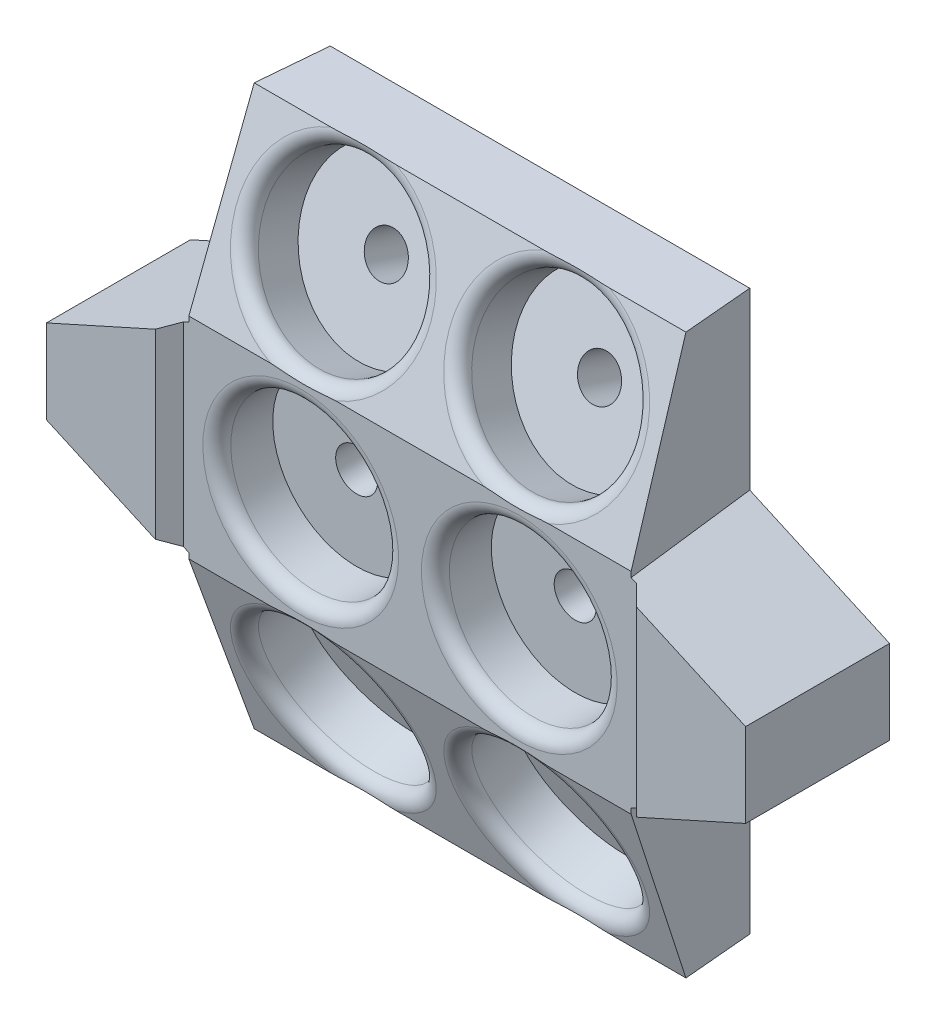
SolidWorks part; units mm, degrees
ref_plane "Front Plane" through (0, 0, 0) normal (0, 0, 1) x (1, 0, 0)
ref_plane "Top Plane" through (0, 0, 0) normal (0, 1, 0) x (1, 0, 0)
ref_plane "Right Plane" through (0, 0, 0) normal (1, 0, 0) x (0, 0, -1)
sketch "Sketch2" plane through (0, 0, 0) normal (0, 1, 0) x (1, 0, 0)
  line L0 (0, 0) -> (30, 0)
  line L1 (30, 0) -> (30.8749, -10)
  line L2 (30.8749, -10) -> (-0.8749, -10)
  line L3 (-0.8749, -10) -> (0, 0)
  dimension "D1" = 95
  dimension "D2" = 95
  dimension "D3" = 30
  dimension "D4" = 10
extrude "Boss-Extrude1" add sketch "Sketch2" along normal blind 40
sketch "Sketch3" plane through (0, 0, 0) normal (1, 0, 0) x (0, 0, -1)
  line L0 (-5, 0) -> (-9.2975, 12.4808)
  line L1 (0, 0) -> (-10, 0) construction
  line L2 (-9.2975, 12.4808) -> (-9.2975, 27.5192)
  line L3 (-9.2975, 27.5192) -> (-5, 40)
  line L4 (0, 40) -> (-10, 40) construction
  line L5 (-5, 0) -> (-10, 0)
  line L6 (-10, 0) -> (-10, 40)
  line L7 (-10, 40) -> (-5, 40)
  dimension "D1" = 161
  dimension "D2" = 161
  dimension "D3" = 13.2
  dimension "D4" = 5
extrude "Cut-Extrude1" cut sketch "Sketch3" against normal through all both and the other way through all
sketch "Sketch5" plane through (0, -1.5392, 4.47) normal (0, -0.3256, 0.9455) x (1, 0, 0)
  line L0 (7.3746, 8.2278) -> (-0.6254, 8.2278) construction
  line L1 (-0.4374, 1.6278) -> (-0.8134, 14.8278) construction
  line L2 (22.6254, 8.2278) -> (30.6254, 8.2278) construction
  line L3 (30.8134, 14.8278) -> (30.4374, 1.6278) construction
  line L4 (7.3746, 8.2278) -> (22.6254, 8.2278) construction
  line L5 (-0.4374, 1.6278) -> (30.4374, 1.6278) construction
  circle A0 centre (7.3746, 8.2278) radius 6
  circle A1 centre (22.6254, 8.2278) radius 6
  dimension "D1" = 12
  dimension "D2" = 8
  dimension "D3" = 6.6
extrude "Cut-Extrude2" cut sketch "Sketch5" against normal blind 4
ref_plane "Plane1" through (0, 20, 0) normal (0, 1, 0) x (1, 0, 0)
mirror "Mirror3" about plane through (0, 20, 0) normal (0, 1, 0) of "Cut-Extrude2"
sketch "Sketch7" plane through (0, 0, 9.2975) normal (0, 0, 1) x (1, 0, 0)
  line L0 (-0.8134, 20) -> (30.8134, 20) construction
  line L1 (-0.8134, 12.4808) -> (-0.8134, 27.5192) construction
  line L2 (30.8134, 27.5192) -> (30.8134, 12.4808) construction
  circle A0 centre (7.1866, 20) radius 6
  circle A1 centre (22.8134, 20) radius 6
  dimension "D1" = 12
  dimension "D2" = 8
  dimension "D3" = 8
extrude "Cut-Extrude3" cut sketch "Sketch7" against normal blind 4
fillet "Fillet1" radius 1 6 edges at (22.6254, 0.5673, 5.1953) (7.3746, 0.5673, 5.1953) (13.1866, 20, 9.2975) (28.8134, 20, 9.2975) (7.3746, 39.4327, 5.1953) (22.6254, 39.4327, 5.1953)
sketch "Sketch9" plane through (0, 0, 0) normal (0, 0, -1) x (-1, 0, 0)
  line L0 (-30, 12.5) -> (-40, 17)
  line L1 (-30, 40) -> (-30, 0) construction
  line L2 (-40, 17) -> (-40, 23)
  line L3 (-40, 23) -> (-30, 27.5)
  line L4 (-30, 27.5) -> (-30, 12.5)
  line L5 (0, 12.5) -> (0, 27.5)
  line L6 (0, 40) -> (0, 0) construction
  line L7 (0, 27.5) -> (10, 23)
  line L8 (10, 23) -> (10, 17)
  line L9 (10, 17) -> (0, 12.5)
  line L10 (-40, 20) -> (10, 20) construction
  point P4 (-30, 20)
  point P13 (0, 20)
  dimension "D1" = 10
  dimension "D2" = 10
  dimension "D3" = 15
  dimension "D4" = 15
  dimension "D5" = 6
  dimension "D6" = 6
extrude "Boss-Extrude2" add sketch "Sketch9" against normal blind 6
sketch "Sketch10" plane through (0, 0, 0) normal (0, 0, -1) x (-1, 0, 0)
  line L0 (-15, 40) -> (-15, 0) construction
  line L1 (-30, 40) -> (0, 40) construction
  line L2 (-30, 0) -> (0, 0) construction
  line L3 (-30, 40) -> (0, 0) construction
  line L4 (-15, 20) -> (10, 20) construction
  line L5 (10, 17) -> (10, 23) construction
  line L6 (-15, 20) -> (-40, 20) construction
  line L7 (-40, 23) -> (-40, 17) construction
  circle A0 centre (-15, 20) radius 15 construction
  circle A1 centre (-15, 37.5) radius 2.1
  circle A2 centre (-15, 2.5) radius 2.1
  circle A3 centre (-35, 20) radius 2.1
  circle A4 centre (5, 20) radius 2.1
  dimension "D1" = 30
  dimension "D2" = 4.2
  dimension "D3" = 20
  dimension "D4" = 20
  dimension "D5" = 17.5
  dimension "D6" = 17.5
extrude "Cut-Extrude5" cut sketch "Sketch10" against normal blind 4
sketch "Sketch11" plane through (0, 0, 5.2975) normal (0, 0, 1) x (1, 0, 0)
  circle A0 centre (7.1866, 20) radius 1.5
  circle A1 centre (22.8134, 20) radius 1.5
  dimension "D1" = 3
  dimension "D2" = 3
extrude "Cut-Extrude6" cut sketch "Sketch11" against normal up to next
sketch "Sketch12" plane through (0, -0.2369, 0.688) normal (0, -0.3256, 0.9455) x (1, 0, 0)
  circle A0 centre (7.3746, 8.2278) radius 1.5
  circle A1 centre (22.6254, 8.2278) radius 1.5
  dimension "D1" = 3
  dimension "D2" = 3
extrude "Cut-Extrude7" cut sketch "Sketch12" against normal up to next
sketch "Sketch13" plane through (0, 4.4767, 13.0012) normal (0, 0.3256, 0.9455) x (1, 0, 0)
  circle A0 centre (22.6254, 29.5929) radius 1.5
  circle A1 centre (7.3746, 29.5929) radius 1.5
  dimension "D1" = 3
  dimension "D2" = 3
extrude "Cut-Extrude8" cut sketch "Sketch13" against normal up to next
sketch "Sketch15" plane through (0, 0, 6) normal (0, 0, 1) x (1, 0, 0)
  line L4 (30.5249, 27.2638) -> (30.5249, 12.7362)
  line L5 (30.5249, 12.7362) -> (40, 17)
  line L6 (40, 17) -> (40, 23)
  line L7 (40, 23) -> (30.5249, 27.2638)
  line L8 (30.5249, 27.2638) -> (30.5249, 12.7362)
  line L9 (30.5249, 12.7362) -> (40, 17)
  line L10 (40, 17) -> (40, 23)
  line L11 (40, 23) -> (30.5249, 27.2638)
  line L12 (-0.5249, 12.7362) -> (-0.5249, 27.2638)
  line L13 (-0.5249, 27.2638) -> (-10, 23)
  line L14 (-10, 23) -> (-10, 17)
  line L15 (-10, 17) -> (-0.5249, 12.7362)
  line L16 (-0.5249, 12.7362) -> (-0.5249, 27.2638)
  line L17 (-0.5249, 27.2638) -> (-10, 23)
  line L18 (-10, 23) -> (-10, 17)
  line L19 (-10, 17) -> (-0.5249, 12.7362)
  dimension "D1" = 0
  dimension "D2" = 0
extrude "Boss-Extrude3" add sketch "Sketch15" along normal up to surface (3.2975 mm away) up to face at (7.1866, 27, 9.2975)
sketch "Sketch17" plane through (0, 0, 9.2975) normal (0, 0, 1) x (1, 0, 0)
  line L0 (31.2134, 13.046) -> (31.2134, 26.954)
  line L1 (-1.2134, 13.046) -> (-1.2134, 26.954)
  line L2 (-0.8134, 12.866) -> (-10, 17) construction
  line L16 (-0.8134, 27.5192) -> (-0.8134, 27.134)
  line L17 (-0.8134, 27.134) -> (-10, 23)
  line L18 (-10, 23) -> (-10, 17)
  line L19 (-10, 17) -> (-0.8134, 12.866)
  line L20 (-0.8134, 12.866) -> (-0.8134, 12.4808)
  line L21 (-0.8134, 12.4808) -> (5.0422, 12.4808)
  line L22 (9.7069, 12.4808) -> (20.2931, 12.4808)
  line L23 (24.9578, 12.4808) -> (30.8134, 12.4808)
  line L24 (30.8134, 12.4808) -> (30.8134, 12.866)
  line L25 (30.8134, 12.866) -> (40, 17)
  line L26 (40, 17) -> (40, 23)
  line L27 (40, 23) -> (30.8134, 27.134)
  line L28 (30.8134, 27.134) -> (30.8134, 27.5192)
  line L29 (30.8134, 27.5192) -> (24.9578, 27.5192)
  line L30 (20.2931, 27.5192) -> (9.7069, 27.5192)
  line L31 (5.0422, 27.5192) -> (-0.8134, 27.5192)
  line L32 (-0.8134, 27.5192) -> (-0.8134, 27.134)
  line L33 (-0.8134, 27.134) -> (-10, 23)
  line L34 (-10, 23) -> (-10, 17)
  line L35 (-10, 17) -> (-0.8134, 12.866)
  line L36 (-0.8134, 12.866) -> (-0.8134, 12.4808)
  line L37 (-0.8134, 12.4808) -> (5.0422, 12.4808)
  line L38 (9.7069, 12.4808) -> (20.2931, 12.4808)
  line L39 (24.9578, 12.4808) -> (30.8134, 12.4808)
  line L40 (30.8134, 12.4808) -> (30.8134, 12.866)
  line L41 (30.8134, 12.866) -> (40, 17)
  line L42 (40, 17) -> (40, 23)
  line L43 (40, 23) -> (30.8134, 27.134)
  line L44 (30.8134, 27.134) -> (30.8134, 27.5192)
  line L45 (30.8134, 27.5192) -> (24.9578, 27.5192)
  line L46 (20.2931, 27.5192) -> (9.7069, 27.5192)
  line L47 (5.0422, 27.5192) -> (-0.8134, 27.5192)
  spline S4 degree 3 poles (-208.2366, 3004.6079) (-16.3502, 9.5456) (-5.3981, 11.6237) (5.82, 12.5282) (6.0142, 12.5451) (6.5971, 12.5879) (6.987, 12.6056) (7.7657, 12.6055) (8.1543, 12.5878) (8.7364, 12.545) (8.9303, 12.5281) (20.1553, 11.6233) (31.1363, 9.6302) (178.0376, 3007.4811) knots -6.969546 -6.969546 -6.969546 -6.969546 0.125 0.125 0.25 0.25 0.5 0.5 0.75 0.75 0.875 0.875 7.983441 7.983441 7.983441 7.983441 only from (5.0422, 12.4808) to (9.7069, 12.4808)
  spline S5 degree 3 poles (-192.9858, 3004.6079) (-1.0994, 9.5456) (9.8528, 11.6237) (21.0709, 12.5282) (21.2651, 12.5451) (21.848, 12.5879) (22.2379, 12.6056) (23.0166, 12.6055) (23.4052, 12.5878) (23.9873, 12.545) (24.1812, 12.5281) (35.4062, 11.6233) (46.3872, 9.6302) (193.2884, 3007.4811) knots -6.969546 -6.969546 -6.969546 -6.969546 0.125 0.125 0.25 0.25 0.5 0.5 0.75 0.75 0.875 0.875 7.983441 7.983441 7.983441 7.983441 only from (20.2931, 12.4808) to (24.9578, 12.4808)
  spline S6 degree 3 poles (238.2366, -2964.6079) (46.3502, 30.4544) (35.3981, 28.3763) (24.18, 27.4718) (23.9858, 27.4549) (23.4029, 27.4121) (23.013, 27.3944) (22.2343, 27.3945) (21.8457, 27.4122) (21.2636, 27.455) (21.0697, 27.4719) (9.8447, 28.3767) (-1.1363, 30.3698) (-148.0376, -2967.4811) knots -6.969546 -6.969546 -6.969546 -6.969546 0.125 0.125 0.25 0.25 0.5 0.5 0.75 0.75 0.875 0.875 7.983441 7.983441 7.983441 7.983441 only from (24.9578, 27.5192) to (20.2931, 27.5192)
  spline S7 degree 3 poles (222.9858, -2964.6079) (31.0994, 30.4544) (20.1472, 28.3763) (8.9291, 27.4718) (8.7349, 27.4549) (8.152, 27.4121) (7.7621, 27.3944) (6.9834, 27.3945) (6.5948, 27.4122) (6.0127, 27.455) (5.8188, 27.4719) (-5.4062, 28.3767) (-16.3872, 30.3698) (-163.2884, -2967.4811) knots -6.969546 -6.969546 -6.969546 -6.969546 0.125 0.125 0.25 0.25 0.5 0.5 0.75 0.75 0.875 0.875 7.983441 7.983441 7.983441 7.983441 only from (9.7069, 27.5192) to (5.0422, 27.5192)
  spline S8 degree 3 poles (5.0422, 12.4808) (5.2374, 12.4808) (5.4316, 12.4969) (5.82, 12.5282) (6.0142, 12.5451) (6.5971, 12.5879) (6.987, 12.6056) (7.7657, 12.6055) (8.1543, 12.5878) (8.7364, 12.545) (8.9303, 12.5281) (9.3183, 12.4968) (9.5123, 12.4808) (9.7069, 12.4808) knots 0 0 0 0 0.125 0.125 0.25 0.25 0.5 0.5 0.75 0.75 0.875 0.875 1 1 1 1
  spline S9 degree 3 poles (20.2931, 12.4808) (20.4882, 12.4808) (20.6824, 12.4969) (21.0709, 12.5282) (21.2651, 12.5451) (21.848, 12.5879) (22.2379, 12.6056) (23.0166, 12.6055) (23.4052, 12.5878) (23.9873, 12.545) (24.1812, 12.5281) (24.5692, 12.4968) (24.7631, 12.4808) (24.9578, 12.4808) knots 0 0 0 0 0.125 0.125 0.25 0.25 0.5 0.5 0.75 0.75 0.875 0.875 1 1 1 1
  spline S10 degree 3 poles (24.9578, 27.5192) (24.7626, 27.5192) (24.5684, 27.5031) (24.18, 27.4718) (23.9858, 27.4549) (23.4029, 27.4121) (23.013, 27.3944) (22.2343, 27.3945) (21.8457, 27.4122) (21.2636, 27.455) (21.0697, 27.4719) (20.6817, 27.5032) (20.4877, 27.5192) (20.2931, 27.5192) knots 0 0 0 0 0.125 0.125 0.25 0.25 0.5 0.5 0.75 0.75 0.875 0.875 1 1 1 1
  spline S11 degree 3 poles (9.7069, 27.5192) (9.5118, 27.5192) (9.3176, 27.5031) (8.9291, 27.4718) (8.7349, 27.4549) (8.152, 27.4121) (7.7621, 27.3944) (6.9834, 27.3945) (6.5948, 27.4122) (6.0127, 27.455) (5.8188, 27.4719) (5.4308, 27.5032) (5.2369, 27.5192) (5.0422, 27.5192) knots 0 0 0 0 0.125 0.125 0.25 0.25 0.5 0.5 0.75 0.75 0.875 0.875 1 1 1 1
  line M24 (-0.8134, 27.134) -> (-10, 23)
  line M25 (-10, 23) -> (-10, 17)
  line M26 (-10, 17) -> (-0.8134, 12.866)
  line M34 (30.8134, 12.866) -> (40, 17)
  line M35 (40, 17) -> (40, 23)
  line M36 (40, 23) -> (30.8134, 27.134)
  dimension "D2" = 0.4
  dimension "D3" = 0.4
  dimension "D1" = 0
extrude "Boss-Extrude4" add sketch "Sketch17" along normal blind 1 contours L0 M34 M35 M36 | L1 M26 M24 M25 region at (35.025, 20, 9.2975) region at (-5.025, 20, 9.2975)
chamfer "Chamfer1" distance 1 angle 45 2 edges at (31.2134, 20, 10.2975) (-1.2134, 20, 10.2975)
